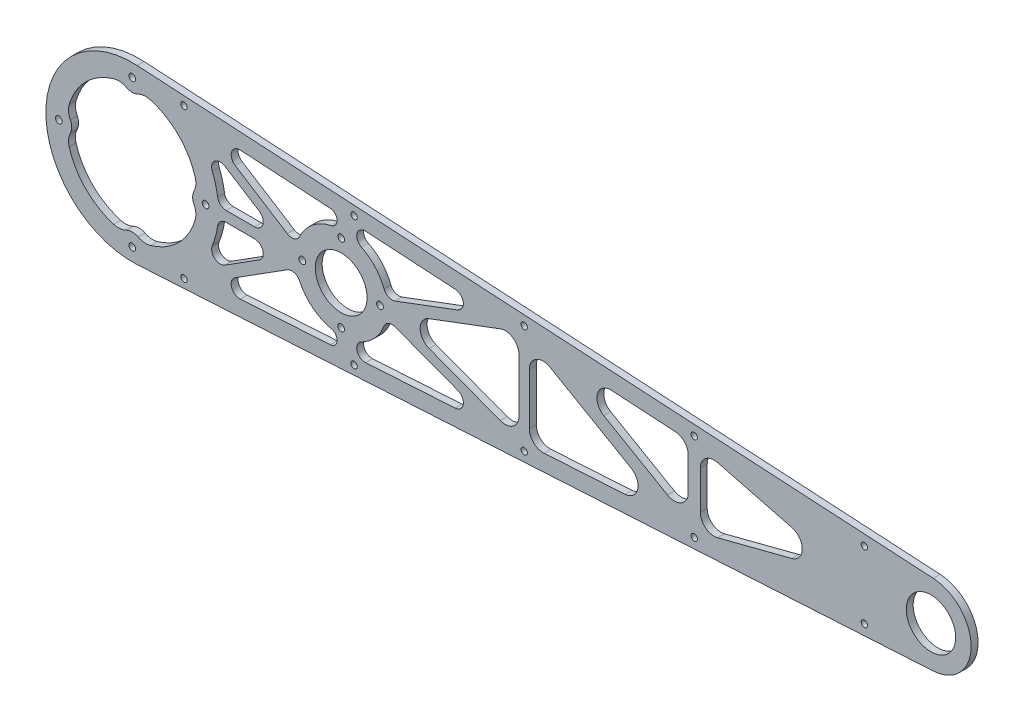
SolidWorks part; units mm, degrees
ref_plane "Front Plane" through (0, 0, 0) normal (0, 0, 1) x (1, 0, 0)
ref_plane "Top Plane" through (0, 0, 0) normal (0, 1, 0) x (1, 0, 0)
ref_plane "Right Plane" through (0, 0, 0) normal (1, 0, 0) x (0, 0, -1)
sketch "Sketch1" plane through (0, 0, 0) normal (0, 0, 1) x (1, 0, 0)
  line L0 (-231.25, 0) -> (231.25, 0) construction
  line L1 (-228.3622, 49.9165) -> (232.595, 23.2486)
  line L2 (-228.3622, -49.9165) -> (232.595, -23.2486)
  line L3 (191.25, 20.6322) -> (-201.25, 43.3396) construction
  circle A0 centre (231.25, 0) radius 14.2875
  arc A1 (232.595, 23.2486) -> (232.595, -23.2486) centre (231.25, 0) cw
  circle A2 centre (-231.25, 0) radius 42.5 construction
  circle A3 centre (-110.25, 0) radius 22.5 construction
  arc A4 (-228.3622, 49.9165) -> (-228.3622, -49.9165) centre (-231.25, 0) ccw
  circle A5 centre (-231.25, 42.5) radius 1.75 construction
  circle A6 centre (-231.25, 0) radius 30
  circle A7 centre (-110.25, 0) radius 15
  circle A8 centre (231.25, 0) radius 35.306 construction
  circle A9 centre (-201.25, 43.3396) radius 1.85
  circle A10 centre (-102.7635, 37.3743) radius 1.85
  circle A11 centre (-4.277, 31.4089) radius 1.85
  circle A12 centre (94.2095, 25.4436) radius 1.85
  circle A13 centre (192.696, 19.4782) radius 1.85
  circle A14 centre (291.1825, 13.5129) radius 1.85 construction
  circle A15 centre (192.696, -19.4782) radius 1.85
  circle A16 centre (94.2095, -25.4436) radius 1.85
  circle A17 centre (-4.277, -31.4089) radius 1.85
  circle A18 centre (-102.7635, -37.3743) radius 1.85
  circle A19 centre (-201.25, -43.3396) radius 1.85
  point P4 (0, 0)
  point P15 (-231.25, 44.25)
  point P16 (-273.75, 0)
  point P17 (-231.25, 50)
  point P18 (-110.25, 22.5)
  point P19 (-231.25, -42.5)
  point P20 (-188.75, 0)
  point P21 (-132.75, 0)
  point P22 (-110.25, -22.5)
  point P23 (-87.75, 0)
  dimension "D2" = 28.575
  dimension "D3" = 85
  dimension "D5" = 45
  dimension "D6" = 3.5
  dimension "D7" = 7.5
  dimension "D8" = 9
  dimension "D9" = 60
  dimension "D10" = 30
  dimension "D11" = 70.612
  dimension "D13" = 3.7
  dimension "D16" = 6
  dimension "D1" = 462.5
  dimension "D4" = 121
  dimension "D12" = 5
  dimension "D14" = 30
  dimension "D15" = 40
extrude "Boss-Extrude1" add sketch "Sketch1" along normal blind 4
sketch "Sketch4" plane through (0, 0, 4) normal (0, 0, 1) x (1, 0, 0)
  point P0 (-231.25, 42.5)
  point P7 (-188.75, 0)
  point P10 (-132.75, 0)
  point P13 (-110.25, 22.5)
  point P16 (-87.75, 0)
  point P19 (-110.25, -22.5)
  point P24 (-273.75, 0)
  point P28 (-231.25, -42.5)
hole_wizard "M3.5 Clearance Hole1" positions "Sketch4" profile "Sketch6" hole size "M3.5" standard "ANSI Metric" end condition up to next
sketch "Sketch6" plane through (-231.25, 42.5, 4) normal (1, 0, 0) x (0, -1, 0)
  line L0 (0, 0) -> (0, 4)
  line L1 (0, 4) -> (1.95, 4)
  line L2 (1.95, 4) -> (1.95, 0)
  line L5 (1.95, 0) -> (0, 0)
  line L11 (0, -6.35) -> (0, 107.95) construction
  dimension "Thru Hole Dia." = 3.9
  dimension "Thru Hole Depth" = 4
sketch "Sketch7" plane through (0, 0, 4) normal (0, 0, 1) x (1, 0, 0)
  line L0 (94.2095, 25.4436) -> (94.2095, -25.4436) construction
  line L1 (94.2095, -25.4436) -> (192.696, 0) construction
  line L2 (192.696, 0) -> (94.2095, 25.4436) construction
  line L3 (192.696, 0) -> (-87.75, 0) construction
  line L4 (192.696, -19.4782) -> (192.696, 19.4782) construction
  line L5 (107.7105, 18.8571) -> (150.7205, 7.7457)
  line L6 (150.7205, -7.7457) -> (107.7105, -18.8571)
  line L7 (97.7095, -11.1115) -> (97.7095, 11.1115)
  line L8 (-4.277, -31.4089) -> (-4.277, 31.4089) construction
  line L9 (-4.277, 31.4089) -> (94.2095, -25.4436) construction
  line L10 (-4.277, 31.4089) -> (94.2095, 25.4436) construction
  line L11 (-4.277, -31.4089) -> (94.2095, -25.4436) construction
  line L12 (-87.75, 0) -> (-102.7635, 37.3743) construction
  line L13 (-102.7635, 37.3743) -> (-4.277, 31.4089) construction
  line L14 (-4.277, 31.4089) -> (-87.75, 0) construction
  line L15 (90.7095, -4.9492) -> (90.7095, 14.1182)
  line L16 (83.1932, 22.1035) -> (46.2904, 24.3387)
  line L17 (41.8072, 9.4249) -> (78.7099, -11.8777)
  line L18 (10.7225, 18.1316) -> (57.6374, -8.9506)
  line L19 (54.1216, -23.8644) -> (7.2067, -26.706)
  line L20 (-1.277, -18.7207) -> (-1.277, 11.2032)
  line L22 (-228.3622, -49.9165) -> (232.595, -23.2486) construction
  line L23 (-7.277, -15.517) -> (-7.277, 15.517)
  line L24 (-18.0944, 23.0044) -> (-59.3325, 7.4875)
  line L25 (-59.3325, -7.4875) -> (-18.0944, -23.0044)
  line L27 (-79.0341, 6.4849) -> (-42.7227, 20.1481)
  line L28 (-44.1812, 29.8186) -> (-96.0994, 32.9633)
  line L32 (-132.75, 0) -> (-188.75, 0) construction
  line L33 (-188.75, 0) -> (-201.25, 43.3396) construction
  line L34 (-201.25, 43.3396) -> (-132.75, 0) construction
  line L35 (-132.75, 0) -> (-102.7635, 37.3743) construction
  line L36 (-102.7635, 37.3743) -> (-201.25, 43.3396) construction
  line L37 (-171.617, 28.141) -> (-141.4788, 9.0727)
  line L39 (-116.5248, 34.2005) -> (-168.6414, 37.3572)
  line L41 (-176.8349, 3) -> (-160.3569, 3)
  line L42 (-157.6835, 12.2253) -> (-177.574, 24.8099)
  line L44 (-116.5248, -34.2005) -> (-168.6414, -37.3572)
  line L45 (-171.617, -28.141) -> (-141.4788, -9.0727)
  line L46 (-157.6835, -12.2253) -> (-177.574, -24.8099)
  line L48 (-176.8349, -3) -> (-160.3569, -3)
  line L50 (-44.1812, -29.8186) -> (-96.0994, -32.9633)
  line L51 (-79.0341, -6.4849) -> (-42.7227, -20.1481)
  line L52 (-102.7635, -37.3743) -> (-110.25, -22.5) construction
  line L53 (-113.0228, -28.1124) -> (-105.6224, -42.8156) construction
  line L54 (-100.7253, -30.3024) -> (-94.7439, -42.1863) construction
  arc A0 (150.7205, 7.7457) -> (150.7205, -7.7457) centre (148.7195, 0) cw
  arc A1 (107.7105, -18.8571) -> (97.7095, -11.1115) centre (105.7095, -11.1115) cw
  arc A2 (107.7105, 18.8571) -> (97.7095, 11.1115) centre (105.7095, 11.1115) ccw
  arc A3 (90.7095, 14.1182) -> (83.1932, 22.1035) centre (82.7095, 14.1182) ccw
  arc A4 (46.2904, 24.3387) -> (41.8072, 9.4249) centre (45.8067, 16.3534) ccw
  arc A5 (90.7095, -4.9492) -> (78.7099, -11.8777) centre (82.7095, -4.9492) cw
  arc A6 (57.6374, -8.9506) -> (54.1216, -23.8644) centre (53.6379, -15.879) cw
  arc A7 (7.2067, -26.706) -> (-1.277, -18.7207) centre (6.723, -18.7207) cw
  arc A8 (10.7225, 18.1316) -> (-1.277, 11.2032) centre (6.723, 11.2032) ccw
  arc A9 (-7.277, -15.517) -> (-18.0944, -23.0044) centre (-15.277, -15.517) cw
  arc A10 (-7.277, 15.517) -> (-18.0944, 23.0044) centre (-15.277, 15.517) ccw
  arc A11 (-59.3325, 7.4875) -> (-59.3325, -7.4875) centre (-56.5152, 0) ccw
  arc A12 (-42.7227, 20.1481) -> (-44.1812, 29.8186) centre (-44.4835, 24.8278) ccw
  arc A18 (-171.617, 28.141) -> (-168.6414, 37.3572) centre (-168.9437, 32.3663) cw
  arc A21 (-160.3569, 3) -> (-157.6835, 12.2253) centre (-160.3569, 8) ccw
  arc A22 (-181.7818, 7.2727) -> (-176.8349, 3) centre (-176.8349, 8) ccw
  arc A23 (-184.8839, 18.7133) -> (-177.574, 24.8099) centre (-180.2473, 20.5846) cw
  arc A26 (-171.617, -28.141) -> (-168.6414, -37.3572) centre (-168.9437, -32.3663) ccw
  arc A27 (-184.8839, -18.7133) -> (-177.574, -24.8099) centre (-180.2473, -20.5846) ccw
  arc A28 (-181.7818, -7.2727) -> (-176.8349, -3) centre (-176.8349, -8) cw
  arc A29 (-160.3569, -3) -> (-157.6835, -12.2253) centre (-160.3569, -8) cw
  circle A30 centre (-110.25, 0) radius 15 construction
  circle A31 centre (-110.25, 0) radius 15 construction
  circle A32 centre (-110.25, 0) radius 22.5 construction
  arc A34 (-85.4703, 9.3925) -> (-98.5366, 23.7707) centre (-110.25, 0) ccw
  arc A37 (-85.4703, 9.3925) -> (-79.0341, 6.4849) centre (-80.7949, 11.1646) ccw
  arc A38 (-42.7227, -20.1481) -> (-44.1812, -29.8186) centre (-44.4835, -24.8278) cw
  arc A39 (-96.0994, -32.9633) -> (-98.5366, -23.7707) centre (-96.3927, -28.1217) cw
  arc A40 (-134.2728, 11.1872) -> (-115.8848, 25.894) centre (-110.25, 0) cw
  arc A41 (-85.4703, -9.3925) -> (-98.5366, -23.7707) centre (-110.25, 0) cw
  arc A42 (-85.4703, -9.3925) -> (-79.0341, -6.4849) centre (-80.7949, -11.1646) cw
  arc A43 (-116.5248, 34.2005) -> (-115.8848, 25.894) centre (-116.779, 30.003) cw
  arc A44 (-134.2728, 11.1872) -> (-141.4788, 9.0727) centre (-138.8054, 13.298) cw
  arc A45 (-116.5248, -34.2005) -> (-115.8848, -25.894) centre (-116.779, -30.003) ccw
  arc A46 (-134.2728, -11.1872) -> (-115.8848, -25.894) centre (-110.25, 0) ccw
  arc A47 (-134.2728, -11.1872) -> (-141.4788, -9.0727) centre (-138.8054, -13.298) ccw
  arc A48 (-96.0994, 32.9633) -> (-98.5366, 23.7707) centre (-96.3927, 28.1217) ccw
  circle A49 centre (-4.277, -31.4089) radius 1.85 construction
  circle A50 centre (-4.277, -31.4089) radius 1.85
  arc A51 (-184.8839, 18.7133) -> (-181.7818, 7.2727) centre (-231.25, 0) cw
  arc A52 (-228.3622, 49.9165) -> (-228.3622, -49.9165) centre (-231.25, 0) ccw construction
  arc A53 (-228.3622, 49.9165) -> (-228.3622, -49.9165) centre (-231.25, 0) ccw
  arc A55 (-184.8839, -18.7133) -> (-181.7818, -7.2727) centre (-231.25, 0) ccw
  point P2 (-182.4224, -10.7642)
  point P18 (0, 0)
  point P36 (180.7024, 0)
  point P59 (-79.2314, 0)
  point P102 (-113.0228, -28.1124)
  dimension "D8" = 8
  dimension "D11" = 5
  dimension "D12" = 5
  dimension "D18" = 5
  dimension "D19" = 5
  dimension "D10" = 4
  dimension "D21" = 5
  dimension "D1" = 3
  dimension "D2" = 7
  dimension "D3" = 8
  dimension "D4" = 8
  dimension "D5" = 8
  dimension "D6" = 6
  dimension "D7" = 6
  dimension "D9" = 8
  dimension "D13" = 8
  dimension "D14" = 5
  dimension "D15" = 6
  dimension "D17" = 6
extrude "Cut-Extrude1" cut sketch "Sketch7" against normal blind 10 contours A55 A27 L46 A29 L48 A28 | A23 A51 A22 L41 A21 L42 | A44 A40 A43 L39 A18 L37 | A46 A47 L45 A26 L44 A45 | A42 A41 A39 L50 A38 L51 | L28 A48 A34 A37 L27 A12 | L24 A11 L25 A9 L23 A10 | L18 A8 L20 A7 L19 A6 | L5 A2 L7 A1 L6 A0 | A5 L15 A3 L16 A4 L17 region at (122.1459, 0, 4) region at (68.375, 8.863, 4) region at (24.042, -7.8996, 4) region at (-30.0623, 0, 4) region at (-71.6765, 22.0808, 4) region at (-143.7382, 26.1619, 4) region at (-171.7996, 12.3824, 4) region at (-143.7382, -26.1619, 4) region at (-171.7996, -12.3824, 4) region at (-71.6765, -22.0808, 4)
sketch "Sketch8" plane through (0, 0, 4) normal (0, 0, 1) x (1, 0, 0)
  arc A0 (-267.0517, -3.3738) -> (-267.0517, 3.3738) centre (-273.75, 0) ccw
  arc A1 (-267.7172, 10.6837) -> (-241.9337, 36.4672) centre (-231.25, 0) cw
  arc A2 (-228.3622, 49.9165) -> (-228.3622, -49.9165) centre (-231.25, 0) ccw construction
  arc A3 (-228.3622, 49.9165) -> (-228.3622, -49.9165) centre (-231.25, 0) ccw
  circle A4 centre (-273.75, 0) radius 1.95 construction
  circle A5 centre (-273.75, 0) radius 1.95
  arc A6 (-234.6238, 35.8017) -> (-227.8762, 35.8017) centre (-231.25, 42.5) ccw
  arc A7 (-220.5663, 36.4672) -> (-194.7828, 10.6837) centre (-231.25, 0) cw
  arc A8 (-195.4483, 3.3738) -> (-195.4483, -3.3738) centre (-188.75, 0) ccw
  arc A9 (-194.7828, -10.6837) -> (-220.5663, -36.4672) centre (-231.25, 0) cw
  arc A10 (-227.8762, -35.8017) -> (-234.6238, -35.8017) centre (-231.25, -42.5) ccw
  arc A11 (-241.9337, -36.4672) -> (-267.7172, -10.6837) centre (-231.25, 0) cw
  arc A12 (-241.9337, 36.4672) -> (-234.6238, 35.8017) centre (-239.1222, 26.8706) cw
  arc A13 (-227.8762, 35.8017) -> (-220.5663, 36.4672) centre (-223.3778, 26.8706) cw
  arc A14 (-194.7828, 10.6837) -> (-195.4483, 3.3738) centre (-204.3794, 7.8722) cw
  arc A15 (-195.4483, -3.3738) -> (-194.7828, -10.6837) centre (-204.3794, -7.8722) cw
  arc A16 (-220.5663, -36.4672) -> (-227.8762, -35.8017) centre (-223.3778, -26.8706) cw
  arc A17 (-234.6238, -35.8017) -> (-241.9337, -36.4672) centre (-239.1222, -26.8706) cw
  arc A18 (-267.0517, -3.3738) -> (-267.7172, -10.6837) centre (-258.1206, -7.8722) ccw
  arc A19 (-267.0517, 3.3738) -> (-267.7172, 10.6837) centre (-258.1206, 7.8722) cw
  point P0 (0, 0)
  point P24 (-231.25, 0)
  dimension "D1" = 12
  dimension "D3" = 10
  dimension "D2" = 4
extrude "Cut-Extrude2" cut sketch "Sketch8" against normal blind 10 contours A11 A10 A9 A8 A7 A6 A1 A0 region at (-231.25, 0, 4)
